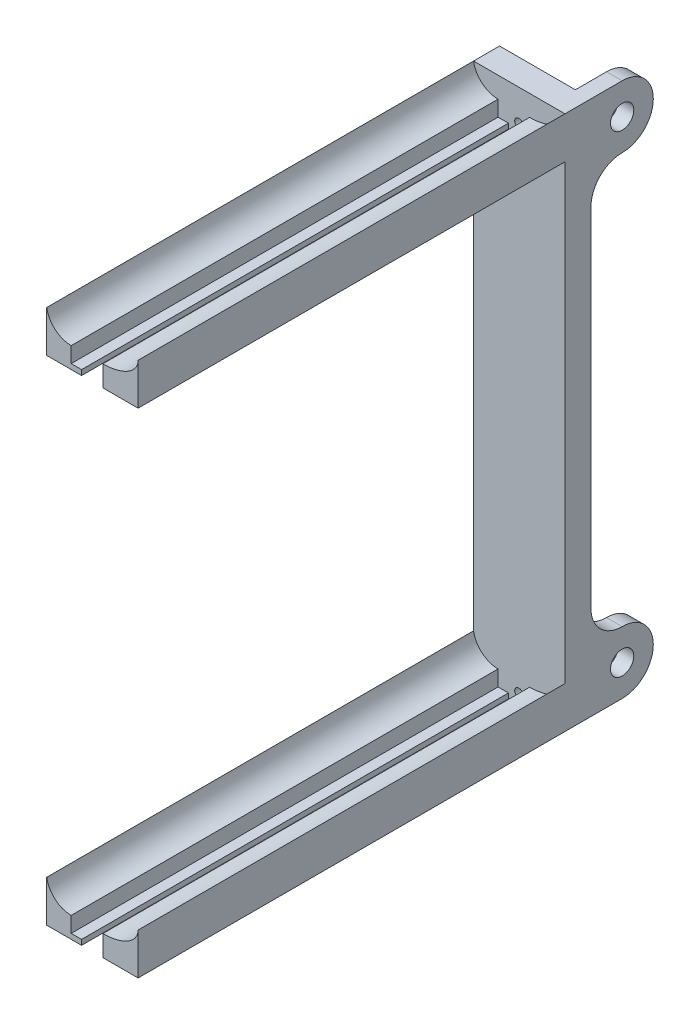
SolidWorks part; units mm, degrees
ref_plane "Front Plane" through (0, 0, 0) normal (0, 0, 1) x (1, 0, 0)
ref_plane "Top Plane" through (0, 0, 0) normal (0, 1, 0) x (1, 0, 0)
ref_plane "Right Plane" through (0, 0, 0) normal (1, 0, 0) x (0, 0, -1)
sketch "Sketch1" plane through (0, 0, 0) normal (0, 0, 1) x (1, 0, 0)
  line L1 (-13.97, -3.175) -> (13.97, -3.175)
  line L2 (-13.97, -3.175) -> (-13.97, 3.175)
  line L3 (-13.97, 3.175) -> (13.97, 3.175)
  line L4 (13.97, -3.175) -> (13.97, 3.175)
  line L5 (-13.97, -3.175) -> (13.97, 3.175) construction
  line L6 (-13.97, 3.175) -> (13.97, -3.175) construction
  point P0 (0, 0)
  dimension "D1" = 27.94
  dimension "D2" = 6.35
extrude "Boss-Extrude1" add sketch "Sketch1" along normal blind 7.9502
sketch "Sketch2" plane through (0, 0, 7.9502) normal (0, 0, 1) x (1, 0, 0)
  line L0 (-3.302, -3.175) -> (-3.302, -1.5875)
  line L1 (-13.97, -3.175) -> (13.97, -3.175) construction
  line L2 (-3.302, -1.5875) -> (-6.477, -1.5875)
  line L3 (-6.477, -1.5875) -> (-6.477, 3.175)
  line L4 (13.97, 3.175) -> (-13.97, 3.175) construction
  line L5 (-6.477, 3.175) -> (-13.97, 3.175)
  line L6 (-13.97, 3.175) -> (-13.97, -3.175)
  line L7 (-13.97, -3.175) -> (-3.302, -3.175)
  line L9 (13.97, -3.175) -> (3.175, -3.175)
  line L10 (13.97, -3.175) -> (13.97, 3.175)
  line L11 (13.97, 3.175) -> (3.175, 3.175)
  line L12 (3.175, -3.175) -> (3.175, 3.175)
  dimension "D1" = 1.5875
  dimension "D2" = 3.302
  dimension "D3" = 3.175
  dimension "D4" = 3.175
extrude "Boss-Extrude2" add sketch "Sketch2" along normal blind 131.2862
sketch "Sketch5" plane through (0, 0, 139.2364) normal (0, 0, 1) x (1, 0, 0)
  line L0 (-13.97, 3.175) -> (-13.97, 9.525)
  line L1 (-13.97, 3.175) -> (-6.477, 3.175)
  line L2 (3.175, 3.175) -> (13.97, 3.175)
  line L3 (13.97, 3.175) -> (13.97, 9.525)
  arc A1 (-6.477, 3.175) -> (-13.97, 9.525) centre (-6.477, 10.7709) cw
  ellipse E0 centre (3.175, 9.525) end of major axis (13.97, 9.525) minor radius 6.35 (3.175, 3.175) -> (13.97, 9.525) ccw
  dimension "D1" = 6.35
  dimension "D2" = 6.35
  dimension "D3" = 6.35
  dimension "D4" = 10.795
extrude "Boss-Extrude3" add sketch "Sketch5" against normal up to surface (131.2862 mm away) up to face at (-2.2013, -0.5292, 7.9502)
sketch "Sketch6" plane through (0, 3.175, 0) normal (0, 1, 0) x (1, 0, 0)
  line L1 (-13.97, -7.9502) -> (13.97, -7.9502)
  line L2 (-13.97, -7.9502) -> (-13.97, 0)
  line L3 (-13.97, 0) -> (13.97, 0)
  line L4 (13.97, -7.9502) -> (13.97, 0)
extrude "Boss-Extrude4" add sketch "Sketch6" along normal blind 144.4752
sketch "Sketch8" plane through (0, 0, 7.9502) normal (0, 0, 1) x (1, 0, 0)
  line L0 (13.97, -3.175) -> (13.97, 9.525) construction
  line L1 (3.175, 3.175) -> (3.175, -3.175) construction
  line L2 (3.175, -3.175) -> (13.97, -3.175) construction
  line L3 (-13.97, -3.175) -> (-3.302, -3.175) construction
  line L4 (-3.302, -3.175) -> (-3.302, -1.5875) construction
  line L5 (-3.302, -1.5875) -> (-6.477, -1.5875) construction
  line L6 (-6.477, -1.5875) -> (-6.477, 3.175) construction
  line L7 (-13.97, 9.525) -> (-13.97, -3.175) construction
  line L8 (13.97, -3.175) -> (13.97, 9.525) construction
  line L9 (3.175, 3.175) -> (3.175, -3.175) construction
  line L10 (3.175, -3.175) -> (13.97, -3.175) construction
  line L11 (-13.97, -3.175) -> (-3.302, -3.175) construction
  line L12 (-3.302, -3.175) -> (-3.302, -1.5875) construction
  line L13 (-3.302, -1.5875) -> (-6.477, -1.5875) construction
  line L14 (-6.477, -1.5875) -> (-6.477, 3.175) construction
  line L15 (-13.97, 9.525) -> (-13.97, -3.175) construction
  line L16 (-13.97, 160.3502) -> (-13.97, 147.6502)
  line L17 (3.175, 147.6502) -> (13.97, 147.6502)
  line L18 (-13.97, 147.6502) -> (-3.302, 147.6502)
  line L19 (-3.302, 149.2377) -> (-6.477, 149.2377)
  line L20 (13.97, 147.6502) -> (13.97, 160.3502)
  line L21 (3.175, 154.0002) -> (3.175, 147.6502)
  line L22 (-3.302, 147.6502) -> (-3.302, 149.2377)
  line L23 (-6.477, 149.2377) -> (-6.477, 154.0002)
  line L24 (-13.97, 147.6502) -> (13.97, 147.6502) construction
  arc A0 (-13.97, 9.525) -> (-6.477, 3.175) centre (-6.477, 10.7709) ccw construction
  arc A1 (-13.97, 9.525) -> (-6.477, 3.175) centre (-6.477, 10.7709) ccw construction
  arc A2 (-13.97, 160.3502) -> (-6.477, 154.0002) centre (-6.477, 161.5961) ccw
  ellipse E0 centre (3.175, 9.525) end of major axis (13.97, 9.525) minor radius 6.35 (3.175, 3.175) -> (13.97, 9.525) ccw construction
  ellipse E1 centre (3.175, 9.525) end of major axis (13.97, 9.525) minor radius 6.35 (3.175, 3.175) -> (13.97, 9.525) ccw construction
  ellipse E2 centre (3.175, 160.3502) end of major axis (13.97, 160.3502) minor radius 6.35 (3.175, 154.0002) -> (13.97, 160.3502) ccw
  dimension "D2" = 7.5959
  dimension "D1" = 12.7
  dimension "D3" = 4.7625
  dimension "D4" = 3.175
  dimension "D5" = 1.5875
extrude "Boss-Extrude5" add sketch "Sketch8" along normal through all separate body
sketch "Sketch9" plane through (0, 147.6502, 0) normal (0, 1, 0) x (1, 0, 0)
  line L4 (-13.97, 0) -> (-13.97, -7.9502)
  line L5 (-13.97, -7.9502) -> (13.97, -7.9502)
  line L6 (13.97, -7.9502) -> (13.97, 0)
  line L7 (13.97, 0) -> (-13.97, 0)
  line L8 (-13.97, 0) -> (-13.97, -7.9502)
  line L9 (-13.97, -7.9502) -> (13.97, -7.9502)
  line L10 (13.97, -7.9502) -> (13.97, 0)
  line L11 (13.97, 0) -> (-13.97, 0)
  dimension "D1" = 0
extrude "Boss-Extrude6" add sketch "Sketch9" along normal through all
sketch "Sketch10" plane through (13.97, 0, 0) normal (1, 0, 0) x (0, 0, -1)
  line L0 (0, -3.175) -> (0, 160.3502) construction
  line L1 (0, -3.175) -> (9.525, -3.175)
  line L2 (9.525, 15.875) -> (0, 15.875)
  line L3 (0, 15.875) -> (0, -3.175)
  arc A0 (9.525, -3.175) -> (9.525, 15.875) centre (9.525, 6.35) ccw
  circle A1 centre (9.525, 6.35) radius 3.556
  dimension "D2" = 19.05
  dimension "D3" = 7.112
  dimension "D1" = 9.525
  dimension "D4" = 9.525
extrude "Boss-Extrude7" add sketch "Sketch10" against normal blind 4.7752
ref_plane "Plane1" through (0, 78.5876, 0) normal (0, 1, 0) x (1, 0, 0)
mirror "Mirror1" about plane through (0, 78.5876, 0) normal (0, 1, 0) of "Boss-Extrude7"
fillet "Fillet1" radius 9.525 2 edges at (11.5824, 141.3002, 0) (11.5824, 15.875, 0)
sketch "Sketch11" plane through (0, 0, 139.2364) normal (0, 0, 1) x (1, 0, 0)
  line L1 (-69.102, 185.4082) -> (87.6201, 185.4082)
  line L2 (-69.102, 185.4082) -> (-69.102, -31.9366)
  line L3 (-69.102, -31.9366) -> (87.6201, -31.9366)
  line L4 (87.6201, 185.4082) -> (87.6201, -31.9366)
extrude "Cut-Extrude1" cut sketch "Sketch11" against normal blind 0.8128
sketch "Sketch12" plane through (0, 0, 7.9502) normal (0, 0, 1) x (1, 0, 0)
  line L0 (-3.302, 147.6502) -> (-3.302, 149.2377) construction
  circle A0 centre (-0.127, 150.8252) radius 1.27
  dimension "D1" = 2.54
  dimension "D2" = 1.5875
  dimension "D3" = 3.175
extrude "Cut-Extrude2" cut sketch "Sketch12" against normal through all
sketch "Sketch14" plane through (0, 0, 7.9502) normal (0, 0, 1) x (1, 0, 0)
  line L0 (-3.302, -3.175) -> (-3.302, -1.5875) construction
  circle A0 centre (-0.127, 0) radius 1.27
  dimension "D3" = 2.54
  dimension "D1" = 1.5875
  dimension "D2" = 3.175
extrude "Cut-Extrude3" cut sketch "Sketch14" against normal through all
sketch "Sketch15" plane through (-13.97, 0, 0) normal (-1, 0, 0) x (0, 0, 1)
  line L0 (138.4236, 147.6502) -> (7.9502, 147.6502) construction
  line L1 (138.4236, 160.3502) -> (138.4236, 147.6502) construction
  line L2 (138.4236, -3.175) -> (0, -3.175) construction
  line L3 (138.4236, 9.525) -> (138.4236, -3.175) construction
  circle A0 centre (132.0736, 150.8252) radius 1.27
  circle A1 centre (132.0736, 0) radius 1.27
  dimension "D3" = 2.54
  dimension "D4" = 2.54
  dimension "D1" = 3.175
  dimension "D2" = 6.35
  dimension "D5" = 3.175
  dimension "D6" = 6.35
extrude "Cut-Extrude4" cut sketch "Sketch15" against normal blind 5.08
